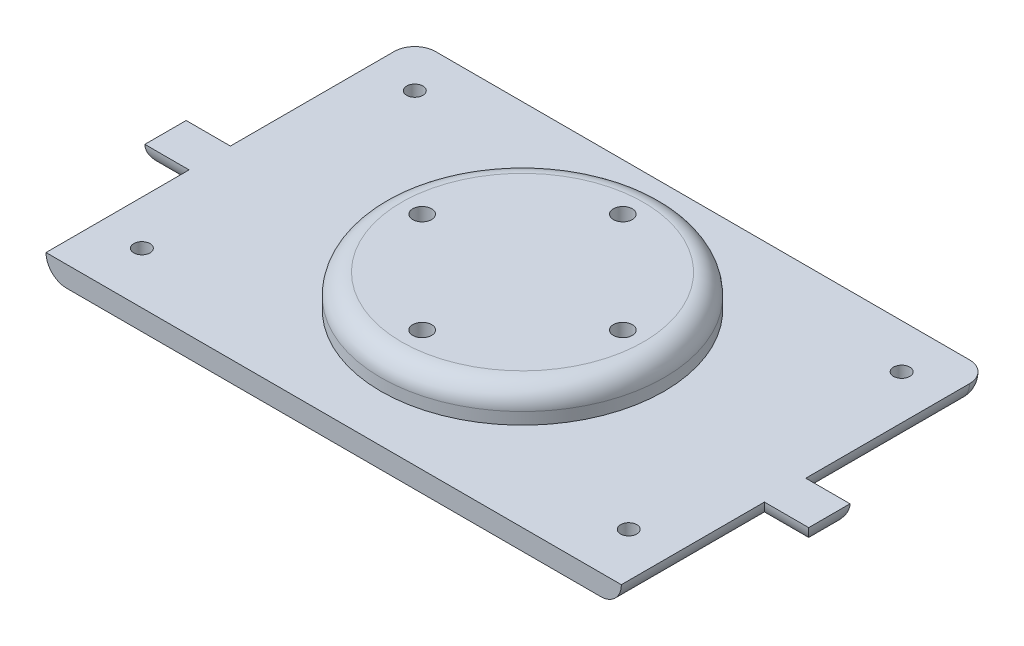
SolidWorks part; units mm, degrees
ref_plane "Front Plane" through (0, 0, 0) normal (0, 0, 1) x (1, 0, 0)
ref_plane "Top Plane" through (0, 0, 0) normal (0, 1, 0) x (1, 0, 0)
ref_plane "Right Plane" through (0, 0, 0) normal (1, 0, 0) x (0, 0, -1)
sketch "Sketch2" plane through (0, 0, 0) normal (0, 1, 0) x (1, 0, 0)
  line L1 (-97.5, 0) -> (97.5, 0)
  line L2 (-97.5, 0) -> (-97.5, -125)
  line L3 (-97.5, -125) -> (97.5, -125)
  line L4 (97.5, 0) -> (97.5, -125)
  point P4 (0, 0)
  dimension "D1" = 195
  dimension "D2" = 125
extrude "Boss-Extrude1" add sketch "Sketch2" along normal blind 57
sketch "Sketch3" plane through (0, 57, 0) normal (0, 1, 0) x (1, 0, 0)
  line L0 (97.5, 0) -> (-97.5, 0) construction
  line L1 (-90.5, 0) -> (90.5, 0)
  line L2 (-90.5, 0) -> (-90.5, -118)
  line L3 (-90.5, -118) -> (90.5, -118)
  line L4 (90.5, 0) -> (90.5, -118)
  line L5 (-97.5, 0) -> (-97.5, -125) construction
  line L6 (97.5, -125) -> (97.5, 0) construction
  line L7 (-97.5, -125) -> (97.5, -125) construction
  dimension "D1" = 7
  dimension "D2" = 7
  dimension "D3" = 7
extrude "Cut-Extrude1" cut sketch "Sketch3" against normal offset from surface (50 mm away) 7 up to face at (0, 0, 62.5)
sketch "Sketch5" plane through (-97.5, 0, 0) normal (-1, 0, 0) x (0, 0, 1)
  line L0 (48.5, 7) -> (48.5, 0)
  line L2 (48.5, 0) -> (62.5, 0)
  line L3 (0, 0) -> (125, 0) construction
  line L4 (62.5, 0) -> (62.5, 57)
  line L5 (0, 57) -> (125, 57) construction
  line L6 (62.5, 57) -> (55.5, 57)
  line L7 (55.5, 57) -> (55.5, 7)
  line L8 (55.5, 7) -> (48.5, 7)
  dimension "D1" = 7
  dimension "D2" = 7
  dimension "D3" = 7
  dimension "D4" = 55.5
extrude "Boss-Extrude2" add sketch "Sketch5" along normal blind 15
sketch "Sketch7" plane through (0, 0, 0) normal (0, -1, 0) x (1, 0, 0)
  line L0 (-97.5, 0) -> (-97.5, 48.5) construction
  line L1 (97.5, 0) -> (-97.5, 0) construction
  line L3 (-97.5, 125) -> (97.5, 125) construction
  circle A0 centre (-82.5, 17.5) radius 2.75
  circle A2 centre (-82.5, 110) radius 2.75
  dimension "D1" = 5.5
  dimension "D4" = 15
  dimension "D2" = 15
  dimension "D3" = 17.5
extrude "Cut-Extrude4" cut sketch "Sketch7" against normal up to next
sketch "Sketch34" plane through (0, 0, 0) normal (0, -1, 0) x (1, 0, 0)
  line L0 (-73.3, 63.75) -> (-51.3, 63.75) construction
  line L1 (-73.3, 42.75) -> (-51.3, 42.75)
  line L2 (-73.3, 42.75) -> (-73.3, 84.75)
  line L3 (-73.3, 84.75) -> (-51.3, 84.75)
  line L4 (-51.3, 42.75) -> (-51.3, 84.75)
  line L5 (-97.5, 0) -> (-97.5, 48.5) construction
  line L6 (-82.5, 17.5) -> (-82.5, 110) construction
  line L7 (-62.3, 42.75) -> (-62.3, 84.75) construction
  circle A0 centre (-57.3, 88.85) radius 2
  circle A1 centre (-67.3, 88.85) radius 2
  circle A2 centre (-78.45, 63.75) radius 2
  circle A3 centre (-46.15, 63.75) radius 2
  circle A4 centre (-57.3, 38.65) radius 2
  circle A5 centre (-67.3, 38.65) radius 2
  point P8 (-82.5, 63.75)
  point P9 (-73.3, 63.75)
  dimension "D4" = 4
  dimension "D5" = 10
  dimension "D1" = 22
  dimension "D2" = 42
  dimension "D3" = 24.2
  dimension "D6" = 25.1
  dimension "D7" = 25.1
  dimension "D8" = 5
  dimension "D9" = 5
  dimension "D10" = 16.15
  dimension "D11" = 16.15
extrude "Cut-Extrude8" cut sketch "Sketch34" against normal up to surface (7 mm away) up to face at (-82.5, 7, 20.25)
mirror "Mirror1" about plane through (0, 0, 0) normal (1, 0, 0) of "Cut-Extrude4", "Boss-Extrude2", "Cut-Extrude8"
mirror "Mirror2" about plane through (0, 0, 0) normal (0, 0, 1) of "Cut-Extrude4", "Cut-Extrude1", "Boss-Extrude1", "Mirror1", "Boss-Extrude2", "Cut-Extrude8"
fillet "Fillet2" radius 7 4 edges at (97.5, 28.5, -125) (-97.5, 28.5, -125) (-97.5, 28.5, 125) (97.5, 28.5, 125)
fillet "Fillet7" radius 7 32 edges at (97.5, 0, 0) (112.5, 0, 55.5) (105, 0, 62.5) (112.5, 3.5, 48.5) (105, 0, 48.5) (97.5, 3.5, 48.5) (-97.5, 0, 0) (-112.5, 0, -55.5) (-105, 0, -62.5) (-112.5, 3.5, -48.5) (-105, 0, -48.5) (-97.5, 3.5, -48.5) (97.5, 0, -90.25) (97.5, 3.5, -48.5) (105, 0, -48.5) (105, 0, -62.5) (112.5, 3.5, -48.5) (112.5, 0, -55.5) (-97.5, 0, 90.25) (-97.5, 3.5, 48.5) (-105, 0, 48.5) (-105, 0, 62.5) (97.5, 0, 90.25) (-97.5, 0, -90.25) (0, 0, -125) (0, 0, 125) (-95.4497, 0, 122.9497) (-95.4497, 0, -122.9497) (-112.5, 3.5, 48.5) (95.4497, 0, -122.9497) (95.4497, 0, 122.9497) (-112.5, 0, 55.5)
sketch "Sketch26" plane through (0, 0, 125) normal (0, 0, 1) x (1, 0, 0)
  line L0 (90.5, 0) -> (-90.5, 0) construction
  line L1 (-90.5, 7) -> (90.5, 7)
  line L2 (83.5, 0) -> (-83.5, 0)
  line L3 (-97.5, 7) -> (-97.5, 57) construction
  line L4 (97.5, 57) -> (97.5, 7) construction
  arc A0 (-90.5, 7) -> (-83.5, 0) centre (-83.5, 7) ccw
  arc A1 (83.5, 0) -> (90.5, 7) centre (83.5, 7) ccw
  dimension "D1" = 7
  dimension "D2" = 7
  dimension "D3" = 7
  dimension "D4" = 7
extrude "Boss-Extrude8" add sketch "Sketch26" against normal up to surface up to face at (0, 2.7751, 122.2249)
sketch "Sketch27" plane through (0, 0, -125) normal (0, 0, -1) x (-1, 0, 0)
  line L0 (90.5, 0) -> (-90.5, 0) construction
  line L1 (-90.5, 7) -> (90.5, 7)
  line L2 (-83.5, 0) -> (83.5, 0)
  line L3 (-97.5, 7) -> (-97.5, 57) construction
  line L5 (97.5, 57) -> (97.5, 7) construction
  arc A0 (-90.5, 7) -> (-83.5, 0) centre (-83.5, 7) ccw
  arc A1 (83.5, 0) -> (90.5, 7) centre (83.5, 7) ccw
  dimension "D1" = 7
  dimension "D3" = 7
  dimension "D4" = 7
  dimension "D2" = 7
extrude "Boss-Extrude9" add sketch "Sketch27" against normal up to next
sketch "Sketch29" plane through (0, 57, 0) normal (0, 1, 0) x (1, 0, 0)
  line L1 (-228.61, 228.4159) -> (231.715, 228.4159)
  line L2 (-228.61, 228.4159) -> (-228.61, -215.9957)
  line L3 (-228.61, -215.9957) -> (231.715, -215.9957)
  line L4 (231.715, 228.4159) -> (231.715, -215.9957)
extrude "Cut-Extrude5" cut sketch "Sketch29" against normal up to surface (50 mm away) up to face at (-57.3, 7, -36.65)
sketch "Sketch30" plane through (0, 7, 0) normal (0, 1, 0) x (1, 0, 0)
  line L0 (-97.5, 0) -> (97.5, 0) construction
  line L1 (97.5, -48.5) -> (97.5, 48.5) construction
  circle A0 centre (0, 64) radius 48
  point P6 (0, 0)
  dimension "D1" = 64
  dimension "D3" = 96
  dimension "D2" = 64
extrude "Boss-Extrude10" add sketch "Sketch30" along normal blind 11
sketch "Sketch31" plane through (0, 0, 0) normal (0, -1, 0) x (1, 0, 0)
  circle A0 centre (0, -64) radius 41
  circle A1 centre (0, -64) radius 48 construction
  dimension "D1" = 82
extrude "Cut-Extrude6" cut sketch "Sketch31" against normal blind 11
sketch "Sketch32" plane through (0, 11, 0) normal (0, -1, 0) x (1, 0, 0)
  line L0 (0, -98) -> (0, -30) construction
  line L1 (-34, -64) -> (34, -64) construction
  circle A0 centre (0, -30) radius 3.2
  circle A1 centre (0, -98) radius 3.2
  circle A2 centre (34, -64) radius 3.2
  circle A3 centre (-34, -64) radius 3.2
  point P8 (0, -64)
  point P10 (0, -64)
  dimension "D1" = 6.4
  dimension "D2" = 30
  dimension "D3" = 68
  dimension "D4" = 68
extrude "Cut-Extrude7" cut sketch "Sketch32" against normal up to surface (7 mm away) up to face at (0, 18, -16)
fillet "Fillet8" radius 7 1 edges at (0, 18, -16)
fillet "Fillet11" radius 6.3 8 edges at (51.3, 3.5, 42.75) (73.3, 3.5, 84.75) (51.3, 3.5, 84.75) (73.3, 3.5, 42.75) (-51.3, 3.5, 42.75) (-73.3, 3.5, 42.75) (-51.3, 3.5, 84.75) (-73.3, 3.5, 84.75)
sketch "Sketch37" plane through (0, 0, 0) normal (0, -1, 0) x (1, 0, 0)
  line L0 (-90.5, -55.5) -> (-90.5, -118) construction
  line L1 (43.5, -100) -> (85.5, -100)
  line L2 (43.5, -100) -> (43.5, -25)
  line L3 (43.5, -25) -> (85.5, -25)
  line L4 (85.5, -100) -> (85.5, -25)
  line L5 (-85.5, -100) -> (-43.5, -100)
  line L6 (-85.5, -100) -> (-85.5, -25)
  line L7 (-85.5, -25) -> (-43.5, -25)
  line L8 (-43.5, -100) -> (-43.5, -25)
  line L9 (90.5, -118) -> (90.5, -55.5) construction
  line L10 (83.5, -125) -> (-83.5, -125) construction
  dimension "D1" = 5
  dimension "D2" = 5
  dimension "D3" = 25
  dimension "D4" = 25
  dimension "D5" = 75
  dimension "D6" = 42
  dimension "D7" = 42
  dimension "D8" = 75
extrude "Boss-Extrude11" add sketch "Sketch37" against normal up to surface (7 mm away)
ref_plane "Plane1" through (0, 0, 0) normal (0, 0, 1) x (1, 0, 0)
sketch "Sketch39" plane through (0, 0, 125) normal (0, 0, 1) x (1, 0, 0)
  line L1 (-134.9183, 66.4256) -> (124.7274, 66.4256)
  line L2 (-134.9183, 66.4256) -> (-134.9183, -49.8833)
  line L3 (-134.9183, -49.8833) -> (124.7274, -49.8833)
  line L4 (124.7274, 66.4256) -> (124.7274, -49.8833)
extrude "Cut-Extrude9" cut sketch "Sketch39" against normal up to surface (125 mm away)
